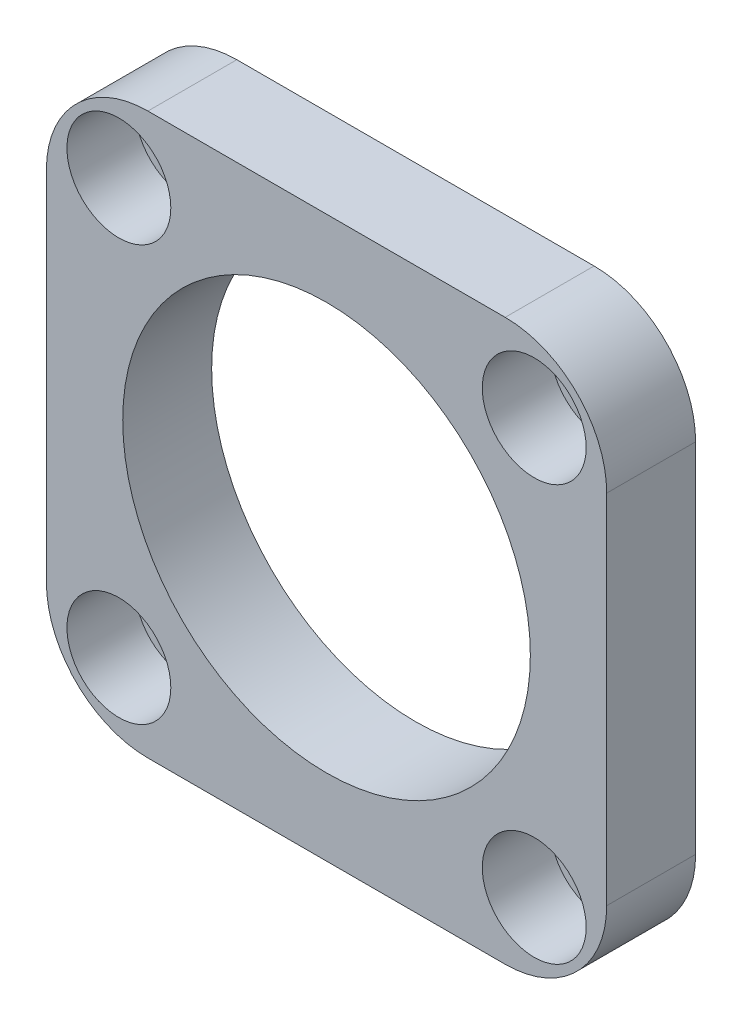
SolidWorks part; units mm, degrees
ref_plane "Front Plane" through (0, 0, 0) normal (0, 0, 1) x (1, 0, 0)
ref_plane "Top Plane" through (0, 0, 0) normal (0, 1, 0) x (1, 0, 0)
ref_plane "Right Plane" through (0, 0, 0) normal (1, 0, 0) x (0, 0, -1)
ref_axis "Axis1" through (0, 0, -88.99) along (0, 0, 1)
sketch "Sketch1" plane through (0, 0, 0) normal (0, 0, 1) x (1, 0, 0)
  line L0 (0, 11.7028) -> (0, -49988.2972) construction
  line L1 (-14.4722, 0) -> (49985.5278, 0) construction
  line L2 (55, 0) -> (-55, 0) construction
  line L3 (0, -55) -> (0, 55) construction
  line L5 (-17.526, 17.526) -> (17.526, 17.526)
  line L6 (-17.526, 17.526) -> (-17.526, -17.526)
  line L7 (-17.526, -17.526) -> (17.526, -17.526)
  line L8 (17.526, 17.526) -> (17.526, -17.526)
  dimension "D1" = 35.052
extrude "Boss-Extrude1" add sketch "Sketch1" along normal blind 5.5626
hole_wizard "CBORE for M3 SHCS3" positions "Sketch3" profile "Sketch2" counterbore size "M3" standard "ANSI Metric" end condition through all
sketch "Sketch3" plane through (0, 0, 5.5626) normal (0, 0, 1) x (1, 0, 0)
  line L0 (-4.98, 0) -> (49995.02, 0) construction
  line L1 (0, 4.9038) -> (0, -49995.0962) construction
  line L2 (3.0594, 0) -> (-3.0594, 0) construction
  line L3 (0, -3.0594) -> (0, 3.0594) construction
  line L4 (-12.9921, 12.9921) -> (12.9921, 12.9921) construction
  line L5 (12.9921, 12.9921) -> (12.9921, -12.9921) construction
  line L6 (12.9921, -12.9921) -> (-12.9921, -12.9921) construction
  line L7 (-12.9921, -12.9921) -> (-12.9921, 12.9921) construction
  point P0 (-12.9921, 12.9921)
  point P1 (12.9921, 12.9921)
  point P3 (12.9921, -12.9921)
  point P5 (-12.9921, -12.9921)
  dimension "D1" = 25.9842
  dimension "D2" = 25.9842
sketch "Sketch2" plane through (-12.9921, 12.9921, 5.5626) normal (1, 0, 0) x (0, -1, 0)
  line L0 (0, 0) -> (0, 5.5626)
  line L1 (1.7, 5.2626) -> (2, 5.5626)
  line L2 (1.7, 5.2626) -> (1.7, 4.27)
  line L3 (1.7, 4.27) -> (3.25, 4.27)
  line L4 (3.25, 4.27) -> (3.25, 0)
  line L5 (3.25, 0) -> (0, 0)
  line L11 (0, -6.35) -> (0, 107.95) construction
  line L12 (2, 5.5626) -> (0, 5.5626)
  line L13 (-1.7, 5.2626) -> (-2, 5.5626) construction
  dimension "Thru Hole Dia." = 3.4
  dimension "Thru Hole Depth" = 5.5626
  dimension "C'Bore Dia." = 6.5
  dimension "C'Bore Depth" = 4.27
  dimension "Far C'Sink Dia." = 4
  dimension "Far C'Sink Angle" = 90
fillet "Fillet1" radius 6.35 4 edges at (17.526, -17.526, 2.7813) (-17.526, -17.526, 2.7813) (-17.526, 17.526, 2.7813) (17.526, 17.526, 2.7813)
sketch "Sketch4" plane through (0, 0, 5.5626) normal (0, 0, 1) x (1, 0, 0)
  circle A0 centre (0, 0) radius 12.9032
  dimension "D1" = 25.8064
extrude "Cut-Extrude1" cut sketch "Sketch4" against normal up to next
chamfer "Chamfer1" distance 0.762 angle 45 2 edges at (12.9032, 0, 0) (12.9032, 0, 5.5626)
sketch "Sketch7" plane through (0, 0, 0) normal (1, 0, 0) x (0, 0, -1)
  line L0 (-7.1628, 0.0883) -> (-7.1628, 50000.0883) construction
  line L2 (-15.1661, 12.6492) -> (49984.8339, 12.6492) construction
  line L4 (-7.6073, 12.6492) -> (-7.1628, 13.4191)
  line L5 (-7.1628, 13.4191) -> (-6.7183, 12.6492)
  line L6 (-6.7183, 12.6492) -> (-7.6073, 12.6492)
  line L7 (-5.5626, 17.526) -> (-5.5626, 11.176) construction
  line L8 (-0.762, 12.9032) -> (-4.8006, 12.9032) construction
  dimension "D1" = 0.254
  dimension "D2" = 60
  dimension "D3" = 0.889
  dimension "D4" = 1.6002
sketch "Sketch9" plane through (0, 0, 5.5626) normal (0, 0, 1) x (1, 0, 0)
  text T0 "SM1A53" font "Arial" height in points 9
extrude "Cut-Extrude3" cut sketch "Sketch9" against normal blind 0.127
sketch "Sketch10" plane through (0, 0, 0) normal (0, 0, -1) x (-1, 0, 0)
  circle A0 centre (0, 0) radius 15
  circle A1 centre (0, 0) radius 13.1
  dimension "D1" = 30
  dimension "D2" = 26.2
extrude "Boss-Extrude2" add sketch "Sketch10" against normal up to surface (5.5626 mm away) up to face at (-0.6604, -15.4046, 5.5626)
sketch "Sketch13" plane through (0, 0, 5.5626) normal (0, 0, 1) x (1, 0, 0)
  line L0 (-11.176, -17.526) -> (11.176, -17.526) construction
  line L1 (-6.8886, -13.526) -> (6.2837, -13.526)
  line L2 (-6.8886, -13.526) -> (-6.8886, -17.526)
  line L3 (-6.8886, -17.526) -> (6.2837, -17.526)
  line L4 (6.2837, -13.526) -> (6.2837, -17.526)
  line L6 (0, -199999.9117) -> (0, 250000.0883) construction
  dimension "D1" = 4
  dimension "D2" = 6.2837
  dimension "D3" = 6.8886
extrude "Boss-Extrude3" add sketch "Sketch13" against normal up to surface (0.127 mm away) up to face at (-5.2011, -15.5631, 5.4356)
sketch "Sketch14" plane through (0, 0, 5.5626) normal (0, 0, 1) x (1, 0, 0)
  circle A0 centre (0, 0) radius 12.75
  circle A1 centre (0, 0) radius 13.9723
  dimension "D1" = 25.5
  dimension "D2" = 27.9445
extrude "Boss-Extrude4" add sketch "Sketch14" against normal up to surface (5.5626 mm away) up to face at (-10.9921, 12.9921, 0)
